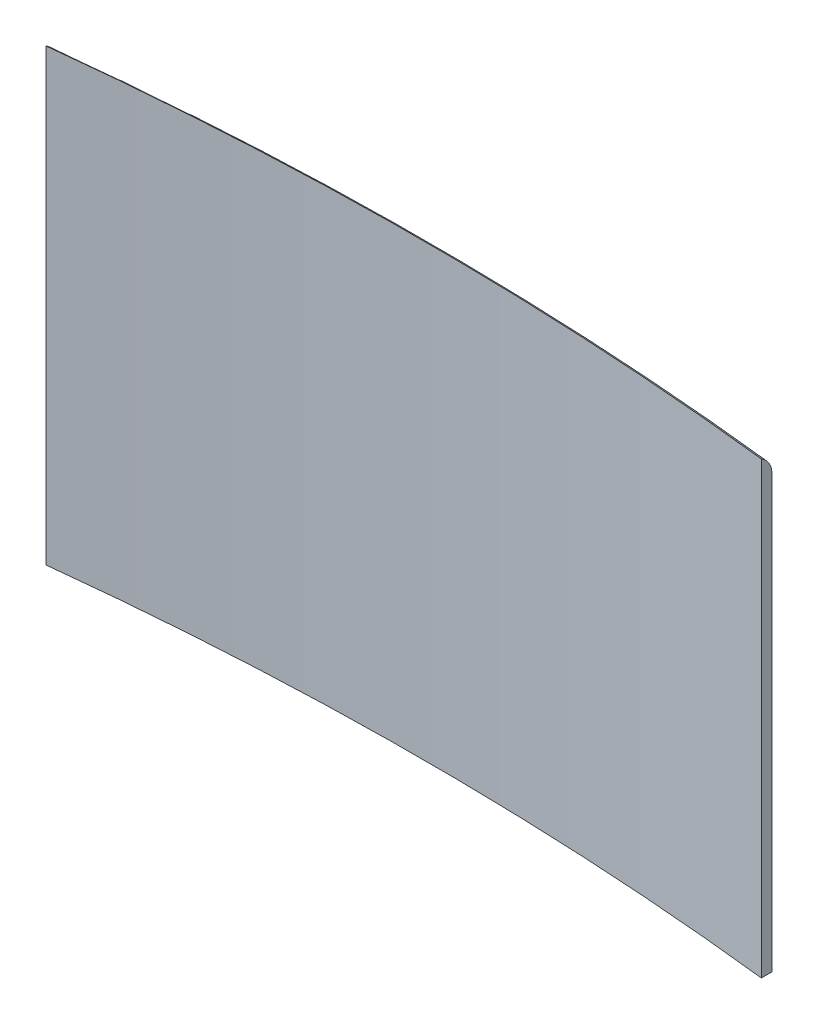
SolidWorks part; units mm, degrees
ref_plane "Front Plane" through (0, 0, 0) normal (0, 0, 1) x (1, 0, 0)
ref_plane "Top Plane" through (0, 0, 0) normal (0, 1, 0) x (1, 0, 0)
ref_plane "Right Plane" through (0, 0, 0) normal (1, 0, 0) x (0, 0, -1)
sketch "Sketch1" plane through (0, 0, 0) normal (0, 1, 0) x (1, 0, 0)
  line L0 (0, 0) -> (0, 1.01)
  line L1 (-68, 1.01) -> (-68, 0)
  line L2 (0, 0) -> (-68, 0) construction
  arc A0 (0, 0) -> (-68, 0) centre (-34, -302.0927) ccw
  arc A1 (0, 1.01) -> (-68, 1.01) centre (-34, -302.0927) ccw
  dimension "D2" = 68
  dimension "D3" = 304
  dimension "D1" = 305.0037
extrude "body" add sketch "Sketch1" along normal blind 42.73
fillet "topEdgeFillet" radius 2 1 edges at (-34, 42.73, -2.911)
